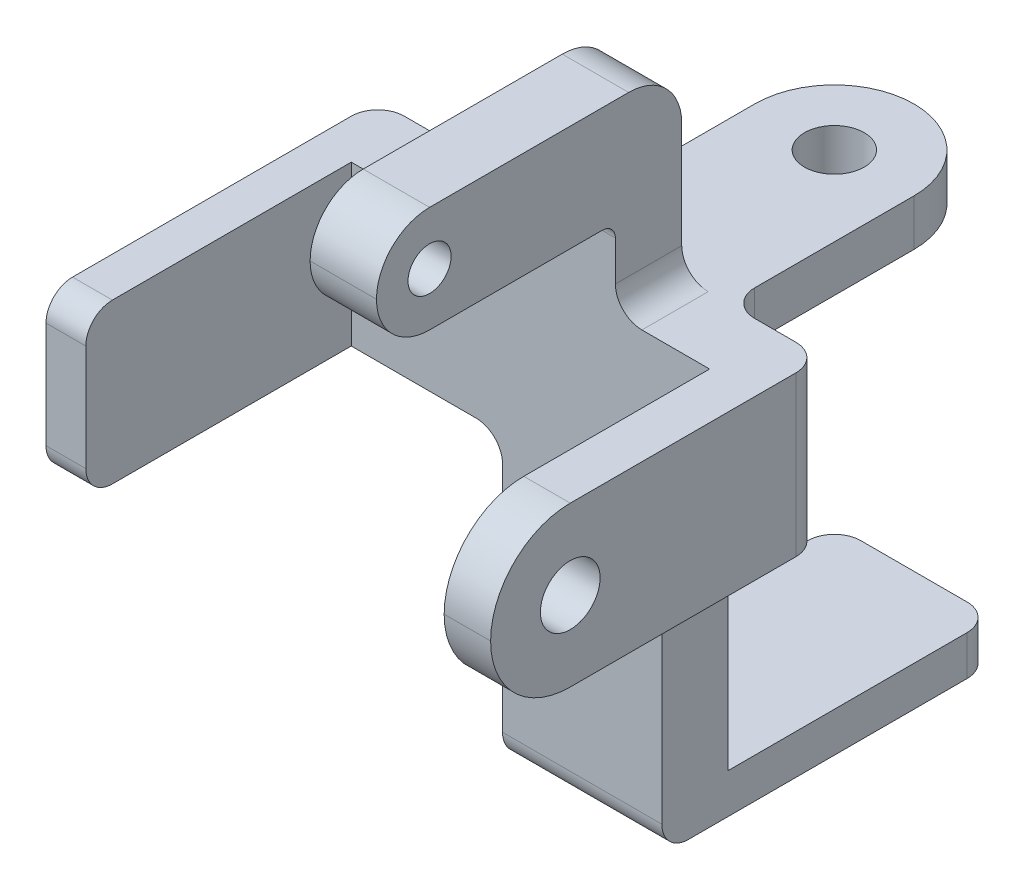
SolidWorks part; units mm, degrees
ref_plane "Front Plane" through (0, 0, 0) normal (0, 0, 1) x (1, 0, 0)
ref_plane "Top Plane" through (0, 0, 0) normal (0, 1, 0) x (1, 0, 0)
ref_plane "Right Plane" through (0, 0, 0) normal (1, 0, 0) x (0, 0, -1)
sketch "Sketch1" plane through (0, 0, 0) normal (0, 0, 1) x (1, 0, 0)
  line L0 (8.5, 33.5) -> (19.1, 33.5)
  line L1 (0, 0) -> (12, 0)
  line L2 (-14.4, 21.5) -> (-14.4, 33.5)
  line L3 (-14.4, 33.5) -> (3.5, 33.5)
  line L4 (19.1, 21.5) -> (19.1, 33.5)
  line L6 (3.5, 33.5) -> (3.5, 47.5)
  line L7 (-14.4, 21.5) -> (0, 21.5)
  line L8 (0, 0) -> (0, 21.5)
  line L9 (19.1, 21.5) -> (12, 21.5)
  line L10 (12, 0) -> (12, 21.5)
  line L11 (3.5, 47.5) -> (8.5, 47.5)
  line L12 (8.5, 33.5) -> (8.5, 47.5)
  dimension "D1" = 33.5
  dimension "D2" = 21.5
  dimension "D3" = 21.5
  dimension "D4" = 14.4
  dimension "D5" = 7.1
  dimension "D6" = 33.5
  dimension "D7" = 10.6
  dimension "D8" = 5
  dimension "D9" = 14
extrude "Boss-Extrude1" add sketch "Sketch1" along normal blind 5
sketch "Sketch3" plane through (0, 0, 5) normal (0, 0, 1) x (1, 0, 0)
  line L0 (3.5, 33.5) -> (-14.4, 33.5) construction
  line L1 (-14.4, 21.5) -> (-11.4, 21.5)
  line L2 (-14.4, 21.5) -> (-14.4, 33.5)
  line L3 (-14.4, 33.5) -> (-11.4, 33.5)
  line L4 (-11.4, 21.5) -> (-11.4, 33.5)
  line L5 (12, 21.5) -> (19.1, 21.5) construction
  line L6 (19.1, 33.5) -> (15.6, 33.5)
  line L7 (19.1, 33.5) -> (19.1, 21.5)
  line L8 (19.1, 21.5) -> (15.6, 21.5)
  line L9 (15.6, 33.5) -> (15.6, 21.5)
  dimension "D1" = 3
  dimension "D2" = 3.5
extrude "Boss-Extrude2" add sketch "Sketch3" along normal blind 20
fillet "Fillet1" radius 6 2 edges at (17.35, 33.5, 25) (17.35, 21.5, 25)
sketch "Sketch4" plane through (0, 0, 0) normal (0, 0, -1) x (-1, 0, 0)
  line L0 (-12, 0) -> (-12, 21.5) construction
  line L1 (0, 0) -> (-12, 0)
  line L2 (0, 0) -> (0, 3)
  line L3 (0, 3) -> (-12, 3)
  line L4 (-12, 0) -> (-12, 3)
  line L5 (-19.1, 33.5) -> (-8.5, 33.5) construction
  line L6 (-12, 33.5) -> (0, 33.5)
  line L7 (-12, 33.5) -> (-12, 30)
  line L8 (-12, 30) -> (0, 30)
  line L9 (0, 33.5) -> (0, 30)
  dimension "D1" = 3
  dimension "D2" = 12
  dimension "D3" = 3.5
  dimension "D4" = 7.1
extrude "Boss-Extrude4" add sketch "Sketch4" along normal blind 20
fillet "Fillet2" radius 6 2 edges at (0, 31.75, -20) (12, 31.75, -20)
sketch "Sketch5" plane through (19.1, 0, 0) normal (1, 0, 0) x (0, 0, -1)
  circle A0 centre (-19, 27.5) radius 2.25
  dimension "D3" = 4.5
  dimension "D1" = 6
  dimension "D2" = 6
extrude "Cut-Extrude2" cut sketch "Sketch5" against normal up to next
sketch "Sketch6" plane through (0, 33.5, 0) normal (0, 1, 0) x (1, 0, 0)
  line L1 (0, 14) -> (0, 0) construction
  circle A0 centre (6, 14) radius 2.25
  dimension "D1" = 4.5
  dimension "D2" = 6
  dimension "D3" = 6
extrude "Cut-Extrude3" cut sketch "Sketch6" against normal up to next
sketch "Sketch7" plane through (8.5, 0, 0) normal (1, 0, 0) x (0, 0, -1)
  line L0 (-23, 39.5) -> (-23, 47.5)
  line L1 (-5, 47.5) -> (-23, 47.5)
  line L2 (-5, 47.5) -> (-5, 39.5)
  line L3 (-5, 39.5) -> (-23, 39.5)
  dimension "D1" = 6
  dimension "D2" = 18
extrude "Boss-Extrude5" add sketch "Sketch7" against normal up to surface (5 mm away) up to face at (3.5, 40.5, 2.5)
fillet "Fillet3" radius 1 1 edges at (6, 39.5, 5)
fillet "Fillet4" radius 2 2 edges at (-14.4, 27.5, 0) (6, 0, 5)
fillet "Fillet5" radius 2 1 edges at (19.1, 27.5, 0)
fillet "Fillet10" radius 2 4 edges at (0, 1.5, -20) (12, 1.5, -20) (-12.9, 21.5, 25) (-12.9, 33.5, 25)
fillet "Fillet11" radius 2 4 edges at (12, 21.5, 2.5) (0, 21.5, 2.5) (3.5, 33.5, 2.5) (8.5, 33.5, 2.5)
fillet "Fillet12" radius 2 2 edges at (0, 31.75, 0) (12, 31.75, 0)
sketch "Sketch8" plane through (8.5, 0, 0) normal (1, 0, 0) x (0, 0, -1)
  line L0 (-23, 47.5) -> (-23, 39.5) construction
  line L1 (-23, 39.5) -> (-6, 39.5) construction
  circle A0 centre (-19, 43.5) radius 1.625
  point P2 (-23, 43.5)
  dimension "D3" = 3.25
  dimension "D1" = 4
  dimension "D2" = 4
fillet "Fillet13" radius 4 3 edges at (6, 47.5, 0) (6, 47.5, 23) (6, 39.5, 23)
extrude "Cut-Extrude4" cut sketch "Sketch8" against normal up to surface (5 mm away) up to face at (3.5, 41.2817, 9.069)
ref_plane "Plane1" through (0, 0, 0) normal (0, 0, -1) x (-1, 0, 0)
